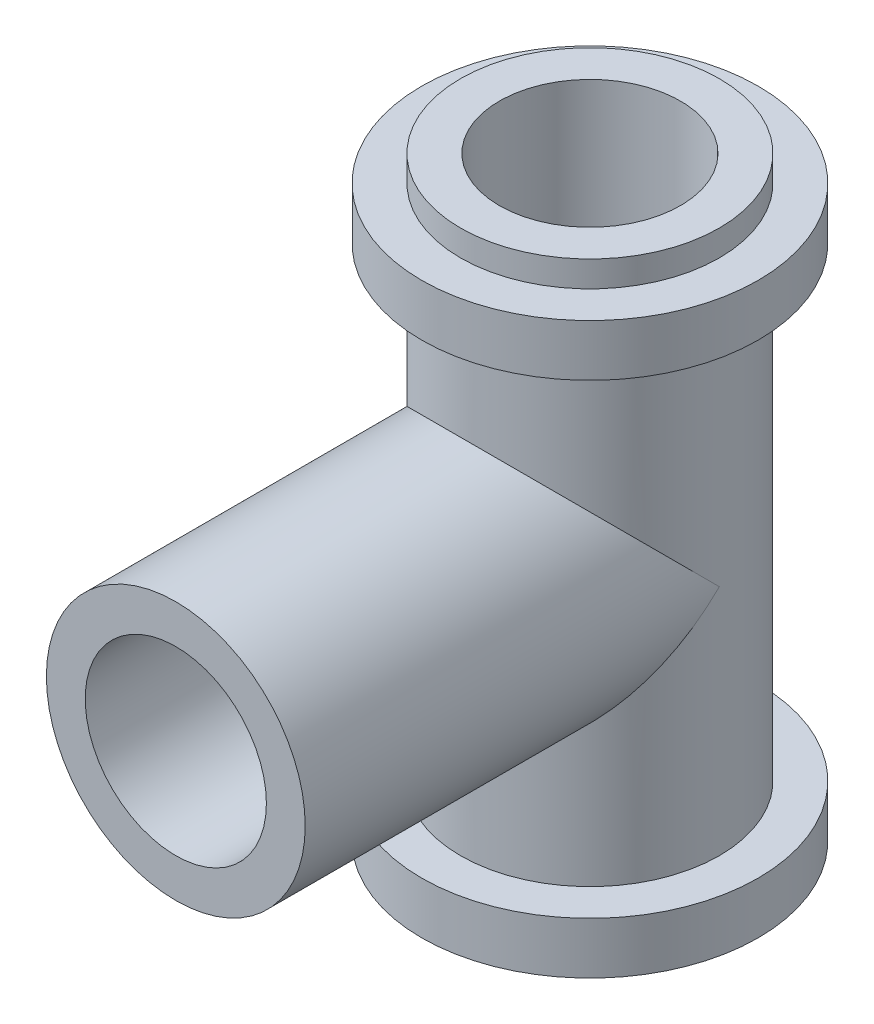
SolidWorks part; units mm, degrees
ref_plane "Front Plane" through (0, 0, 0) normal (0, 0, 1) x (1, 0, 0)
ref_plane "Top Plane" through (0, 0, 0) normal (0, 1, 0) x (1, 0, 0)
ref_plane "Right Plane" through (0, 0, 0) normal (1, 0, 0) x (0, 0, -1)
sketch "Sketch2" plane through (0, 0, 0) normal (0, 1, 0) x (1, 0, 0)
  circle A0 centre (0, 0) radius 25
  dimension "D1" = 50
extrude "Boss-Extrude1" add sketch "Sketch2" along normal blind 120
sketch "Sketch3" plane through (0, 0, 0) normal (0, 0, 1) x (1, 0, 0)
  circle A0 centre (0, 60) radius 25
  point P2 (0, 0)
  dimension "D1" = 50
  dimension "D2" = 60
extrude "Boss-Extrude2" add sketch "Sketch3" along normal blind 80
shell "Shell1" thickness 7.5 removed face at (25, 60, 80) removed face at (0, 120, 25) removed face at (0, 0, 25)
sketch "Sketch4" plane through (0, 0, 0) normal (0, -1, 0) x (1, 0, 0)
  circle A0 centre (0, 0) radius 32.5
  dimension "D1" = 65
extrude "Boss-Extrude3" add sketch "Sketch4" against normal blind 10 from offset 5 offset against normal yes
ref_plane "Plane1" through (0, 60, 0) normal (0, 1, 0) x (1, 0, 0)
mirror "Mirror1" about plane through (0, 60, 0) normal (0, 1, 0) of "Boss-Extrude3"
sketch "Sketch5" plane through (0, 5, 0) normal (0, -1, 0) x (1, 0, 0)
  circle A1 centre (0, 0) radius 17.5
  circle A2 centre (0, 0) radius 17.5
  dimension "D1" = 0
extrude "Cut-Extrude1" cut sketch "Sketch5" against normal through all
